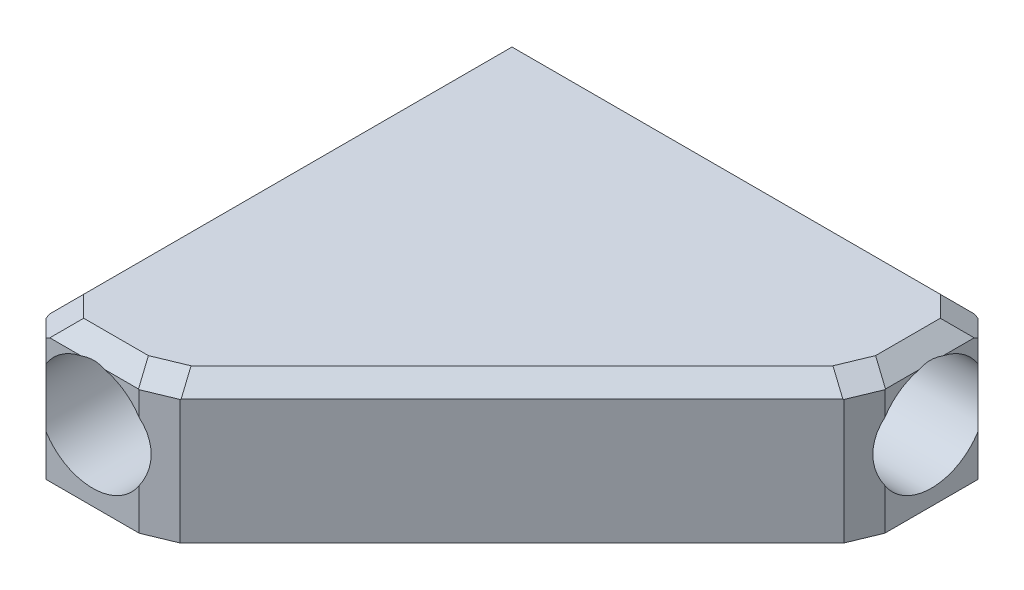
SolidWorks part; units mm, degrees
ref_plane "Front Plane" through (0, 0, 0) normal (0, 0, 1) x (1, 0, 0)
ref_plane "Top Plane" through (0, 0, 0) normal (0, 1, 0) x (1, 0, 0)
ref_plane "Right Plane" through (0, 0, 0) normal (1, 0, 0) x (0, 0, -1)
sketch "Sketch1" plane through (0, 0, 0) normal (0, 1, 0) x (1, 0, 0)
  line L1 (7.5, -5) -> (-7.5, -5)
  line L2 (7.5, -5) -> (7.5, 5)
  line L3 (7.5, 5) -> (-7.5, 5)
  line L4 (-7.5, -5) -> (-7.5, 5)
  line L5 (7.5, -5) -> (-7.5, 5) construction
  line L6 (7.5, 5) -> (-7.5, -5) construction
  line L8 (-7.5, 5) -> (-7.5, 20)
  line L9 (-7.5, 20) -> (7.5, 20)
  line L10 (7.5, 5) -> (7.5, 20)
  line L11 (7.5, 5) -> (17.5, 5)
  line L13 (7.5, 20) -> (17.5, 20)
  line L14 (17.5, 5) -> (17.5, 20)
  point P0 (0, 0)
  dimension "D1" = 10
  dimension "D2" = 15
  dimension "D3" = 15
  dimension "D4" = 10
extrude "Boss-Extrude1" add sketch "Sketch1" along normal blind 16.7 contours L4 L1 L2 L3 | L3 L10 L9 L8 | L11 L14 L13 L10
sketch "Sketch2" plane through (0, 0, 5) normal (0, 0, 1) x (1, 0, 0)
  line L0 (0, 0) -> (0, 16.7) construction
  line L1 (7.5, 0) -> (-7.5, 0) construction
  line L2 (7.5, 16.7) -> (-7.5, 16.7) construction
  circle A0 centre (0, 8.35) radius 6.5
  dimension "D1" = 13
extrude "Cut-Extrude1" cut sketch "Sketch2" against normal offset from surface (8.3 mm away) 16.7 up to face at (5, 8.35, -20)
sketch "Sketch3" plane through (17.5, 0, 0) normal (1, 0, 0) x (0, 0, -1)
  line L0 (12.5, 0) -> (12.5, 16.7) construction
  line L1 (5, 0) -> (20, 0) construction
  line L2 (5, 16.7) -> (20, 16.7) construction
  circle A0 centre (12.5, 8.35) radius 6.5
  dimension "D1" = 13
extrude "Cut-Extrude2" cut sketch "Sketch3" against normal offset from surface (8.3 mm away) 16.7 up to face at (-7.5, 8.35, -7.5)
sketch "Sketch4" plane through (0, 0, 0) normal (0, -1, 0) x (1, 0, 0)
  line L0 (0, 5) -> (0, -20) construction
  line L1 (7.5, 5) -> (-7.5, 5) construction
  line L2 (-7.5, -20) -> (17.5, -20) construction
  line L3 (17.5, -12.5) -> (-7.5, -12.5) construction
  line L4 (17.5, -5) -> (17.5, -20) construction
  line L5 (-7.5, 5) -> (-7.5, -20) construction
  circle A0 centre (0, -12.5) radius 6.5
  dimension "D1" = 13
extrude "Cut-Extrude3" cut sketch "Sketch4" against normal offset from surface (14.7 mm away) 2 up to face at (5.8333, 16.7, -6.6667)
fillet "Fillet8" radius 2 6 edges at (-7.5, 8.35, -20) (7.5, 8.35, -5) (-7.5, 0, -7.5) (-7.5, 16.7, -7.5) (5, 0, -20) (5, 16.7, -20)
sketch "Sketch5" plane through (0, 0, 5) normal (0, 0, 1) x (1, 0, 0)
  line L0 (-7.5, 14.7) -> (-7.5, 2)
  line L1 (-7.5, 2) -> (-5.5, 0)
  line L2 (-5.5, 0) -> (5.5, 0)
  line L6 (5.5, 16.7) -> (-5.5, 16.7)
  line L7 (-5.5, 16.7) -> (-7.5, 14.7)
  line L8 (5.5, 16.7) -> (7.5, 16.7)
  line L9 (7.5, 16.7) -> (7.5, 0)
  line L10 (7.5, 0) -> (5.5, 0)
  circle A0 centre (0, 8.35) radius 6.5
extrude "Boss-Extrude2" add sketch "Sketch5" along normal blind 32
sketch "Sketch6" plane through (17.5, 0, 0) normal (1, 0, 0) x (0, 0, -1)
  line L2 (7, 0) -> (18, 0)
  line L3 (18, 0) -> (20, 2)
  line L4 (20, 2) -> (20, 14.7)
  line L5 (20, 14.7) -> (18, 16.7)
  line L6 (18, 16.7) -> (7, 16.7)
  line L8 (7, 16.7) -> (5, 16.7)
  line L9 (5, 16.7) -> (5, 0)
  line L10 (5, 0) -> (7, 0)
  circle A0 centre (12.5, 8.35) radius 6.5
extrude "Boss-Extrude3" add sketch "Sketch6" along normal blind 32
sketch "Sketch7" plane through (0, 16.7, 0) normal (0, 1, 0) x (1, 0, 0)
  line L0 (7.5, -37) -> (7.5, 3)
  line L1 (7.5, 3) -> (9.5, 5)
  line L2 (9.5, 5) -> (49.5, 5)
  line L7 (7.5, -37) -> (49.5, 5)
extrude "Boss-Extrude4" add sketch "Sketch7" against normal up to surface (16.7 mm away) up to face at (15.1973, 0, 2.6973)
chamfer "Chamfer1" distance 2 angle 45 3 edges at (49.5, 16.7, -11.5) (28.5, 16.7, 16) (1, 16.7, 37)
chamfer "Chamfer2" distance 2 8 edges at (48.5, 15.7, -5.4142) (48.5, 15.7, -19) (-6.5, 15.7, 36) (7.5, 7.35, 37) (7.0858, 15.7, 36) (49.5, 8.35, -20) (49.5, 7.35, -5) (-7.5, 8.35, 37)
